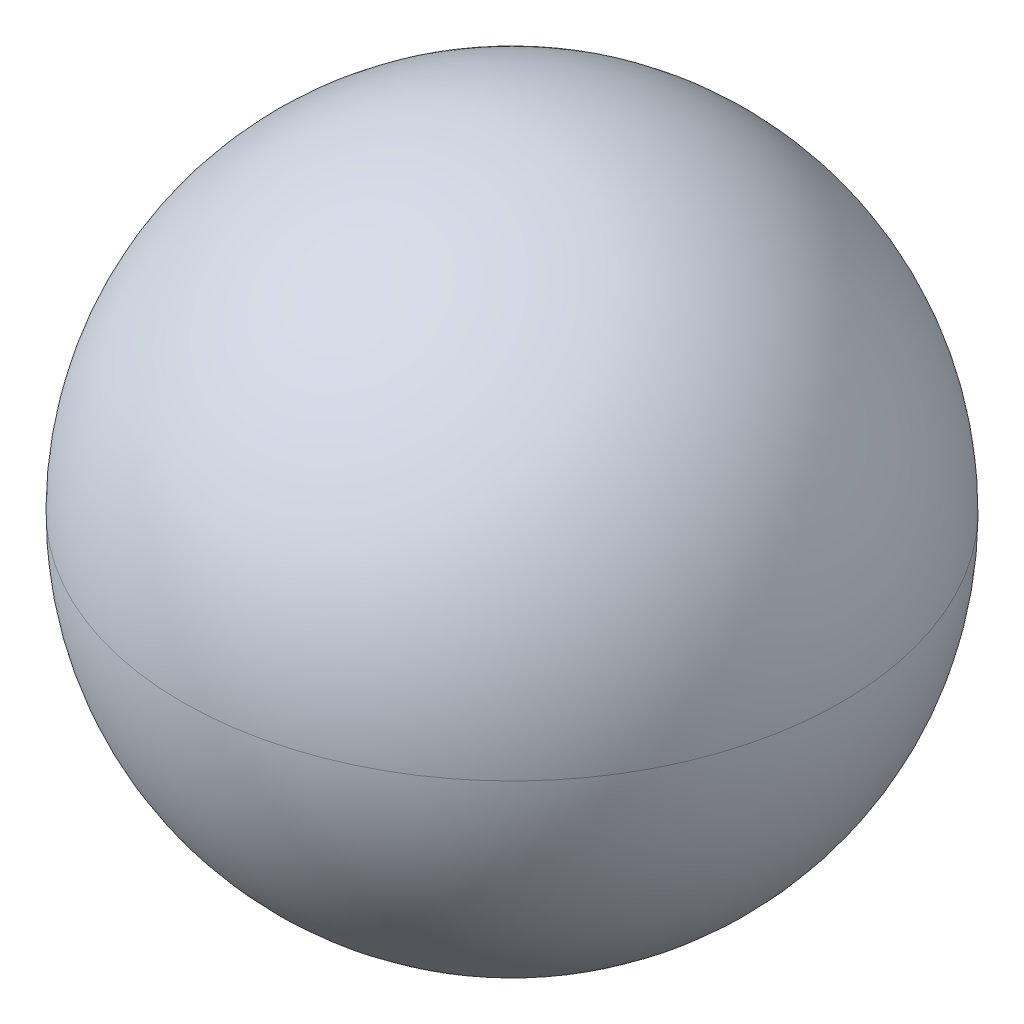
SolidWorks part; units mm, degrees
material "201 Acero inoxidable recocido (SS)"
ref_plane "Alzado" through (0, 0, 0) normal (0, 0, 1) x (1, 0, 0)
ref_plane "Planta" through (0, 0, 0) normal (0, 1, 0) x (1, 0, 0)
ref_plane "Vista lateral" through (0, 0, 0) normal (1, 0, 0) x (0, 0, -1)
sketch "Croquis1" plane through (0, 0, 0) normal (0, 1, 0) x (1, 0, 0)
  circle A0 centre (0, 0) radius 11.7
  dimension "D1" = 23.4
extrude "Saliente-Extruir1" add sketch "Croquis1" along normal blind 23.4
fillet "Redondeo1" radius 11.7 2 edges at (0, 0, 11.7) (0, 23.4, 11.7)
sketch "Croquis2" plane through (0, 0, 0) normal (0, 1, 0) x (1, 0, 0)
  circle A0 centre (0, 0) radius 3
  dimension "D1" = 6
extrude "Cortar-Extruir1" cut sketch "Croquis2" along normal blind 8 contours A0
